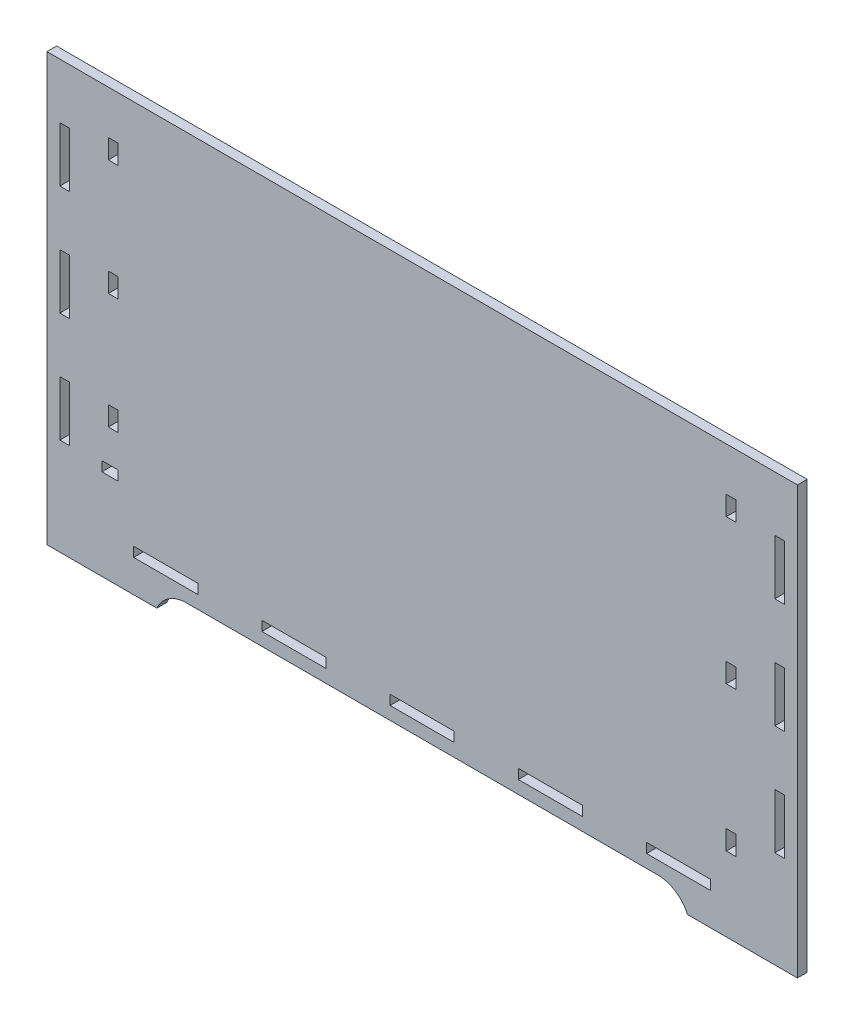
SolidWorks part; units mm, degrees
ref_plane "Front Plane" through (0, 0, 0) normal (0, 0, 1) x (1, 0, 0)
ref_plane "Top Plane" through (0, 0, 0) normal (0, 1, 0) x (1, 0, 0)
ref_plane "Right Plane" through (0, 0, 0) normal (1, 0, 0) x (0, 0, -1)
sketch "Sketch1" plane through (0, 0, 0) normal (0, 0, 1) x (1, 0, 0)
  line L1 (-218, -119) -> (218, -119)
  line L2 (-218, -119) -> (-218, 119)
  line L3 (-218, 119) -> (218, 119)
  line L4 (218, -119) -> (218, 119)
  line L5 (-218, -119) -> (218, 119) construction
  line L6 (-218, 119) -> (218, -119) construction
  point P0 (0, 0)
  dimension "D1" = 436
  dimension "D2" = 238
extrude "Boss-Extrude1" add sketch "Sketch1" along normal blind 6 contours L2 L3 L4 L1
sketch "Sketch2" plane through (0, 0, 0) normal (0, 0, -1) x (-1, 0, 0)
  line L1 (188, 92) -> (194, 92)
  line L2 (188, 92) -> (188, 80)
  line L3 (188, 80) -> (194, 80)
  line L4 (194, 92) -> (194, 80)
  line L5 (188, 20.5) -> (194, 20.5)
  line L6 (188, 20.5) -> (188, 8.5)
  line L7 (188, 8.5) -> (194, 8.5)
  line L8 (194, 20.5) -> (194, 8.5)
  line L9 (188, -51) -> (194, -51)
  line L10 (188, -51) -> (188, -63)
  line L11 (188, -63) -> (194, -63)
  line L12 (194, -51) -> (194, -63)
  line L13 (188, -83) -> (198, -83)
  line L14 (188, -83) -> (188, -89)
  line L15 (188, -89) -> (198, -89)
  line L16 (198, -83) -> (198, -89)
extrude "Cut-Extrude1" cut sketch "Sketch2" against normal blind 6
sketch "Sketch3" plane through (-218, 0, 0) normal (-1, 0, 0) x (0, 0, 1)
  line L0 (0, -119) -> (0, 119) construction
  line L1 (6, 119) -> (0, 119)
  line L2 (6, 119) -> (6, 85)
  line L3 (6, 85) -> (0, 85)
  line L4 (0, 119) -> (0, 85)
  line L5 (6, -119) -> (6, 119) construction
  line L6 (0, 85) -> (6, 85)
  line L7 (0, 85) -> (0, 51)
  line L8 (0, 51) -> (6, 51)
  line L9 (6, 85) -> (6, 51)
  line L11 (6, 51) -> (0, 51)
  line L12 (6, 51) -> (6, 17)
  line L13 (6, 17) -> (0, 17)
  line L14 (0, 51) -> (0, 17)
  line L15 (0, 17) -> (6, 17)
  line L16 (0, 17) -> (0, -17)
  line L17 (0, -17) -> (6, -17)
  line L18 (6, 17) -> (6, -17)
  line L19 (6, -17) -> (0, -17)
  line L20 (6, -17) -> (6, -51)
  line L21 (6, -51) -> (0, -51)
  line L22 (0, -17) -> (0, -51)
  line L23 (0, -51) -> (6, -51)
  line L24 (0, -51) -> (0, -85)
  line L25 (0, -85) -> (6, -85)
  line L26 (6, -51) -> (6, -85)
  line L27 (6, -85) -> (0, -85)
  line L28 (6, -85) -> (6, -119)
  line L29 (6, -119) -> (0, -119)
  line L30 (0, -85) -> (0, -119)
  line M17 (0, 119) -> (0, -119)
  line M18 (0, -119) -> (6, -119)
  line M19 (6, -119) -> (6, 119)
  line M20 (6, 119) -> (0, 119)
extrude "Boss-Extrude2" add sketch "Sketch3" along normal blind 6 contours L3 M19 M20 M17 | L13 L8 M19 M17 | L21 L17 M19 M17 | L25 M17 M18 M19 region at (-218, 102, 3) region at (-218, 34, 3) region at (-218, -34, 3) region at (-218, -102, 3)
mirror "Mirror1" about plane through (0, 0, 0) normal (1, 0, 0) of "Boss-Extrude2"
sketch "Sketch4" plane through (0, -119, 0) normal (0, -1, 0) x (1, 0, 0)
  line L0 (-224, 6) -> (224, 6) construction
  line L1 (-218, 0) -> (-178.3636, 0)
  line L2 (-218, 0) -> (-218, 6)
  line L3 (-218, 6) -> (-178.3636, 6)
  line L4 (-178.3636, 0) -> (-178.3636, 6)
  line L5 (-224, 0) -> (224, 0) construction
  line L7 (-178.3636, 6) -> (-178.3636, 0)
  line L9 (-178.3636, 6) -> (-178.3636, 0)
  line L11 (-178.3636, 0) -> (-138.7273, 0)
  line L12 (-178.3636, 0) -> (-178.3636, 6)
  line L13 (-178.3636, 6) -> (-138.7273, 6)
  line L14 (-138.7273, 0) -> (-138.7273, 6)
  line L15 (-138.7273, 6) -> (-99.0909, 6)
  line L16 (-138.7273, 6) -> (-138.7273, 0)
  line L17 (-138.7273, 0) -> (-99.0909, 0)
  line L18 (-99.0909, 6) -> (-99.0909, 0)
  line L19 (-99.0909, 0) -> (-59.4545, 0)
  line L20 (-99.0909, 0) -> (-99.0909, 6)
  line L21 (-99.0909, 6) -> (-59.4545, 6)
  line L22 (-59.4545, 0) -> (-59.4545, 6)
  line L23 (-59.4545, 6) -> (-19.8182, 6)
  line L24 (-59.4545, 6) -> (-59.4545, 0)
  line L25 (-59.4545, 0) -> (-19.8182, 0)
  line L26 (-19.8182, 6) -> (-19.8182, 0)
  line L27 (-19.8182, 0) -> (19.8182, 0)
  line L28 (-19.8182, 0) -> (-19.8182, 6)
  line L29 (-19.8182, 6) -> (19.8182, 6)
  line L30 (19.8182, 0) -> (19.8182, 6)
  line L31 (19.8182, 6) -> (59.4545, 6)
  line L32 (19.8182, 6) -> (19.8182, 0)
  line L33 (19.8182, 0) -> (59.4545, 0)
  line L34 (59.4545, 6) -> (59.4545, 0)
  line L35 (59.4545, 0) -> (99.0909, 0)
  line L36 (59.4545, 0) -> (59.4545, 6)
  line L37 (59.4545, 6) -> (99.0909, 6)
  line L38 (99.0909, 0) -> (99.0909, 6)
  line L39 (99.0909, 6) -> (138.7273, 6)
  line L40 (99.0909, 6) -> (99.0909, 0)
  line L41 (99.0909, 0) -> (138.7273, 0)
  line L42 (138.7273, 6) -> (138.7273, 0)
  line L43 (138.7273, 0) -> (178.3636, 0)
  line L44 (138.7273, 0) -> (138.7273, 6)
  line L45 (138.7273, 6) -> (178.3636, 6)
  line L46 (178.3636, 0) -> (178.3636, 6)
  line L47 (178.3636, 6) -> (218, 6)
  line L48 (178.3636, 6) -> (178.3636, 0)
  line L49 (178.3636, 0) -> (218, 0)
  line L50 (218, 6) -> (218, 0)
  line L51 (218, 0) -> (224, 0)
  line L52 (218, 0) -> (218, 6)
  line L53 (218, 6) -> (224, 6)
  line L54 (224, 0) -> (224, 6)
  line L55 (-218, 0) -> (-224, 0)
  line L56 (-218, 0) -> (-218, 6)
  line L57 (-218, 6) -> (-224, 6)
  line L58 (-224, 0) -> (-224, 6)
  line M42 (-224, 0) -> (224, 0)
  line M43 (224, 0) -> (224, 6)
  line M44 (224, 6) -> (-224, 6)
  line M45 (-224, 6) -> (-224, 0)
  dimension "D1" = 6
extrude "Boss-Extrude3" add sketch "Sketch4" along normal blind 6 contours L4 L2 M42 M44 | L2 M42 M44 M45 | L18 L14 M44 M42 | L26 L22 M44 M42 | L34 L30 M44 M42 | L42 L38 M44 M42 | L50 L46 M44 M42 | L50 M44 M42 M43 region at (-198.1818, -119, 3) region at (-221, -119, 3) region at (-118.9091, -119, 3) region at (-39.6364, -119, 3) region at (39.6364, -119, 3) region at (118.9091, -119, 3) region at (198.1818, -119, 3) region at (221, -119, 3)
sketch "Sketch5" plane through (0, 0, 0) normal (0, 0, -1) x (-1, 0, 0)
  line L1 (224, -125) -> (-224, -125)
  line L2 (224, -125) -> (224, -133)
  line L3 (224, -133) -> (-224, -133)
  line L4 (-224, -125) -> (-224, -133)
  line L5 (-224, -133) -> (-164, -133)
  line L6 (-224, -133) -> (-224, -145)
  line L7 (-224, -145) -> (-164, -145)
  line L8 (-164, -133) -> (-164, -145)
  line L9 (224, -133) -> (164, -133)
  line L10 (224, -133) -> (224, -145)
  line L11 (224, -145) -> (164, -145)
  line L12 (164, -133) -> (164, -145)
  dimension "D1" = 8
  dimension "D2" = 12
  dimension "D3" = 60
extrude "Boss-Extrude4" add sketch "Sketch5" against normal blind 6 contours L3 L12 L11 L10 | L8 L3 L6 L7 | L1 L4 L3 L2 region at (0, -129, 0) region at (-194, -139, 0) region at (194, -139, 0)
fillet "Fillet1" radius 20 2 edges at (164, -133, 3) (-164, -133, 3)
sketch "Sketch6" plane through (-224, 0, 0) normal (-1, 0, 0) x (0, 0, 1)
  line L1 (0, -145) -> (6, -145)
  line L2 (0, -145) -> (0, 119)
  line L3 (0, 119) -> (6, 119)
  line L4 (6, -145) -> (6, 119)
extrude "Boss-Extrude5" add sketch "Sketch6" along normal blind 8
mirror "Mirror2" about plane through (0, 0, 0) normal (1, 0, 0) of "Boss-Extrude5"
sketch "Sketch7" plane through (0, 0, 0) normal (0, 0, -1) x (-1, 0, 0)
  line L0 (-194, -9.5) -> (-188, -9.5) construction
  line L1 (-194, 92) -> (-188, 92)
  line L2 (-194, 92) -> (-194, 80)
  line L3 (-194, 80) -> (-188, 80)
  line L4 (-188, 92) -> (-188, 80)
  line L5 (-194, 2.5) -> (-188, 2.5)
  line L6 (-194, 2.5) -> (-194, -9.5)
  line L7 (-194, -9.5) -> (-188, -9.5)
  line L8 (-188, 2.5) -> (-188, -9.5)
  line L9 (-188, -9.5) -> (-188, 2.5) construction
  line L10 (-194, -87) -> (-188, -87)
  line L11 (-194, -87) -> (-194, -99)
  line L12 (-194, -99) -> (-188, -99)
  line L13 (-188, -87) -> (-188, -99)
extrude "Cut-Extrude2" cut sketch "Sketch7" against normal through all contours L4 L1 L2 L3 | L8 L5 L6 L7 | L13 L10 L11 L12 region at (191, 86, 0) region at (191, -3.5, 0) region at (191, -93, 0)
